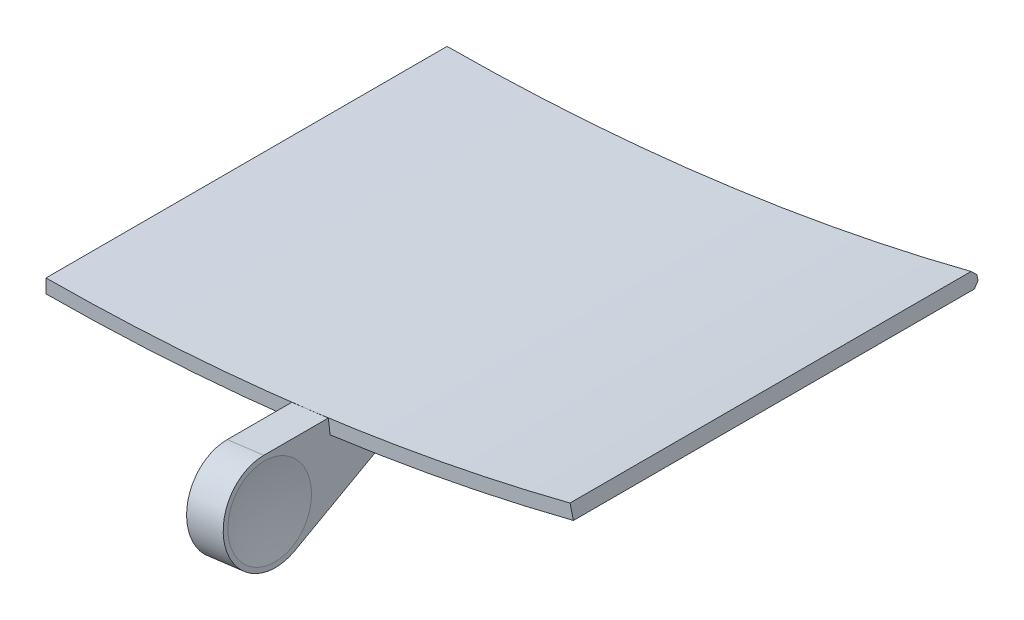
SolidWorks part; units mm, degrees
ref_plane "前视基准面" through (0, 0, 0) normal (0, 0, 1) x (1, 0, 0)
ref_plane "上视基准面" through (0, 0, 0) normal (0, 1, 0) x (1, 0, 0)
ref_plane "右视基准面" through (0, 0, 0) normal (1, 0, 0) x (0, 0, -1)
other "Configuration Table"
sketch "草图1" plane through (0, 0, 0) normal (0, 0, 1) x (1, 0, 0)
  line L0 (0, -235) -> (0, -236.5)
  line L1 (59.1966, -227.422) -> (59.5745, -228.8736)
  arc A0 (0, -235) -> (59.1966, -227.422) centre (0, 0) ccw
  arc A1 (0, -236.5) -> (59.5745, -228.8736) centre (0, 0) ccw
  dimension "D1" = 470
  dimension "D2" = 473
  dimension "D3" = 14.59
  dimension "D4" = 1.5
extrude "凸台-拉伸1" add sketch "草图1" along normal blind 44
chamfer "倒角1" distance 0.5 angle 45 4 edges at (0, -235.75, 0) (30.0303, -234.5857, 0) (59.3855, -228.1478, 0) (29.8398, -233.0978, 0)
sketch "草图4" plane through (0, 0, 44) normal (0, 0, 1) x (1, 0, 0)
  line L0 (1.2, -234.9969) -> (1.2, -236.497)
  line L1 (59.5745, -228.8736) -> (59.1966, -227.422)
  line L2 (58.0345, -227.7213) -> (58.4124, -229.173)
  line L3 (0, -235) -> (0, -236.5)
  line L4 (59.5745, -228.8736) -> (59.1966, -227.422)
  line L5 (0, -235) -> (0, -236.5)
  arc A0 (0, -235) -> (59.1966, -227.422) centre (0, 0) ccw construction
  arc A1 (0, -236.5) -> (59.5745, -228.8736) centre (0, 0) ccw construction
  arc A2 (58.0345, -227.7213) -> (59.1966, -227.422) centre (0, 0) ccw
  arc A3 (58.4124, -229.173) -> (59.5745, -228.8736) centre (0, 0) ccw
  arc A4 (0, -235) -> (59.1966, -227.422) centre (0, 0) ccw
  arc A5 (0, -236.5) -> (59.5745, -228.8736) centre (0, 0) ccw
  arc A6 (0, -235) -> (1.2, -234.9969) centre (0, 0) ccw
  arc A7 (0, -236.5) -> (1.2, -236.497) centre (0, 0) ccw
  dimension "D1" = 0
  dimension "D2" = 1.2
  dimension "D3" = 1.2
extrude "切除-拉伸1" cut sketch "草图4" against normal through all
ref_plane "基准面4" through (0, 0, 0) normal (-0.9919, -0.127, 0) x (0, 0, 1)
sketch "草图5" plane through (0, 0, 0) normal (-0.9919, -0.127, 0) x (0, 0, 1)
  line L0 (44, -235) -> (51, -235)
  line L1 (29, -235.235) -> (48.8826, -244.5295)
  line L2 (29, -235.235) -> (44, -235.235)
  line L3 (44, -235.235) -> (44, -235)
  line L6 (44, -234.735) -> (44, -233.2471) construction
  arc A0 (48.8826, -244.5295) -> (51, -235) centre (51, -240) ccw
  dimension "D1" = 10
  dimension "D2" = 0.5
  dimension "D3" = 15
  dimension "D4" = 7
extrude "凸台-拉伸3" add sketch "草图5" along normal blind 2 and the other way blind 2
ref_plane "基准面5" through (31.1096, -243.0169, 0) normal (0.127, -0.9919, 0) x (-0.9919, -0.127, 0)
ref_plane "基准面6" through (30.4747, -238.0573, 0) normal (0.127, -0.9919, 0) x (-0.9919, -0.127, 0)
sketch "草图6" plane through (30.4747, -238.0573, 0) normal (0.127, -0.9919, 0) x (-0.9919, -0.127, 0)
  line L0 (2, -51) -> (50002, -51) construction
  line L2 (-2, -56) -> (2, -56) construction
  line L3 (-2, -51) -> (-2, -55.5)
  line L4 (-2, -48.8826) -> (-2, -56) construction
  line L5 (-2, -51) -> (-1.4, -51)
  line L6 (0, -56) -> (0, 49944) construction
  line L7 (-2, -51) -> (-50002, -51) construction
  line L8 (2, -51) -> (1.4, -51)
  line L9 (2, -51) -> (2, -55.5)
  arc A0 (-2, -55.5) -> (-1.4, -51) centre (-21.3965, -50.6238) ccw
  arc A1 (2, -55.5) -> (1.4, -51) centre (21.3965, -50.6238) cw
  point P13 (0, -56)
  dimension "D2" = 20
  dimension "D1" = 5
  dimension "D3" = 0.6
  dimension "D4" = 4.5
revolve "切除-旋转2" cut sketch "草图6" angle 360 about L0
